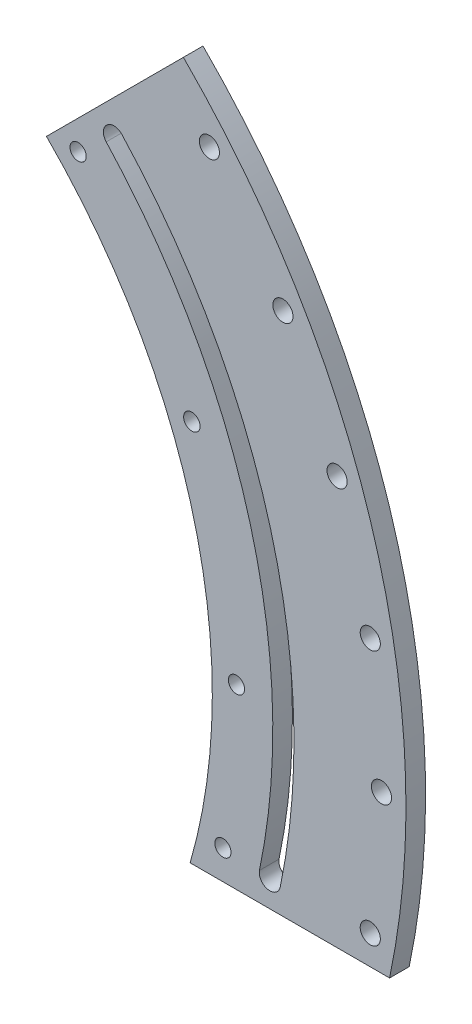
SolidWorks part; units mm, degrees
material "6061-T6 (SS)"
ref_plane "Front Plane" through (0, 0, 0) normal (0, 0, 1) x (1, 0, 0)
ref_plane "Top Plane" through (0, 0, 0) normal (0, 1, 0) x (1, 0, 0)
ref_plane "Right Plane" through (0, 0, 0) normal (1, 0, 0) x (0, 0, -1)
sketch "Sketch1" plane through (0, 0, 0) normal (0, 0, 1) x (1, 0, 0)
  line L0 (0, 0) -> (177.8, 0) construction
  line L1 (177.8, 0) -> (183.3563, 0) construction
  line L2 (0, 0) -> (191.1772, 6.6761) construction
  line L3 (0, 0) -> (182.7798, 182.7798) construction
  line L4 (184.7031, 10.1184) -> (184.959, 2.7905) construction
  line L5 (184.959, 2.7905) -> (191.4331, -0.6518) construction
  line L6 (191.4331, -0.6518) -> (197.6513, 3.2337) construction
  line L7 (197.6513, 3.2337) -> (197.3954, 10.5616) construction
  line L8 (197.3954, 10.5616) -> (190.9213, 14.0039) construction
  line L9 (190.9213, 14.0039) -> (184.7031, 10.1184) construction
  line L10 (139.9034, 130.462) -> (0, 0) construction
  line L11 (0, 0) -> (176.7324, 73.2049) construction
  line L12 (183.3563, 0) -> (183.3563, -50.8) construction
  line L13 (176.1785, -50.8) -> (183.3563, -50.8) construction
  line L14 (0, 0) -> (186.7878, -41.275) construction
  line L15 (0, 0) -> (203.2, 0) construction
  line L16 (203.2, 0) -> (209.55, 0) construction
  line L17 (209.55, 0) -> (228.6, 0) construction
  line L18 (228.6, 0) -> (238.125, 0) construction
  line L19 (0, 0) -> (238.125, 0) construction
  line L20 (0, 0) -> (234.5073, 41.35) construction
  line L21 (176.1785, -50.8) -> (240.7615, -50.8)
  line L22 (0, 0) -> (238.125, 0) construction
  line L23 (0, 0) -> (234.5073, -41.35) construction
  line L24 (129.6524, 129.6524) -> (173.9925, 173.9925)
  line L25 (153.8492, 142.2731) -> (149.1871, 137.9618) construction
  line L26 (198.8628, -41.7593) -> (205.1195, -42.8625) construction
  arc A0 (183.3563, 0) -> (129.6524, 129.6524) centre (0, 0) ccw
  arc A1 (184.9438, 0) -> (130.775, 130.775) centre (0, 0) ccw construction
  circle A3 centre (191.1772, 6.6761) radius 6.35 construction
  circle A4 centre (191.1772, 6.6761) radius 2.6289
  circle A5 centre (139.9034, 130.462) radius 2.6289
  circle A6 centre (176.7324, 73.2049) radius 2.667
  arc A7 (183.3563, 0) -> (176.1785, -50.8) centre (0, 0) cw
  circle A8 centre (186.7878, -41.275) radius 2.6289
  arc A9 (203.2, 0) -> (143.6841, 143.6841) centre (0, 0) ccw construction
  arc A10 (209.55, 0) -> (148.1742, 148.1742) centre (0, 0) ccw construction
  arc A11 (228.6, 0) -> (161.6446, 161.6446) centre (0, 0) ccw construction
  arc A12 (238.125, 0) -> (168.3798, 168.3798) centre (0, 0) ccw construction
  circle A13 centre (238.125, 0) radius 3.2639
  circle A14 centre (234.5073, 41.35) radius 3.2639
  circle A15 centre (223.7643, 81.4435) radius 3.2639
  circle A16 centre (206.2223, 119.0625) radius 3.2639
  circle A17 centre (182.4143, 153.0638) radius 3.2639
  arc A18 (240.7615, -50.8) -> (173.9925, 173.9925) centre (0, 0) ccw
  circle A19 centre (234.5073, -41.35) radius 3.2639
  arc A20 (209.55, 0) -> (153.8492, 142.2731) centre (0, 0) ccw construction
  arc A21 (149.1871, 137.9618) -> (203.2, 0) centre (0, 0) cw construction
  arc A22 (209.55, 0) -> (205.1195, -42.8625) centre (0, 0) cw construction
  arc A23 (203.2, 0) -> (198.8628, -41.7593) centre (0, 0) cw construction
  arc A24 (153.8492, 142.2731) -> (149.1871, 137.9618) centre (151.5181, 140.1174) ccw construction
  arc A25 (205.1195, -42.8625) -> (198.8628, -41.7593) centre (201.9911, -42.3109) cw construction
  arc A26 (202.946, 0) -> (198.6134, -41.711) centre (0, 0) cw
  arc A27 (205.3689, -42.9106) -> (198.6134, -41.711) centre (201.9911, -42.3109) cw
  arc A28 (209.804, 0) -> (205.3689, -42.9106) centre (0, 0) cw
  arc A29 (209.804, 0) -> (154.0357, 142.4455) centre (0, 0) ccw
  arc A30 (154.0357, 142.4455) -> (149.0006, 137.7893) centre (151.5181, 140.1174) ccw
  arc A31 (149.0006, 137.7893) -> (202.946, 0) centre (0, 0) cw
  point P9 (135.2593, 126.1313)
  point P20 (170.8657, 70.7749)
  point P27 (179.0372, -39.5623)
  dimension "D3" = 1.5875
  dimension "D4" = 12.7
  dimension "D6" = 5.2578
  dimension "D8" = 5.2578
  dimension "D12" = 5.334
  dimension "D14" = 50.8
  dimension "D15" = 5.2578
  dimension "D19" = 6.35
  dimension "D20" = 19.05
  dimension "D22" = 6.5278
  dimension "D26" = 7.9375
  dimension "D30" = 7.9375
  dimension "D31" = 7.9375
  dimension "D33" = 183.3562
  dimension "D1" = 177.8
  dimension "D2" = 5.5562
  dimension "D5" = 2
  dimension "D7" = 45
  dimension "D9" = 6.35
  dimension "D10" = 2
  dimension "D11" = 22.5
  dimension "D13" = 6.35
  dimension "D16" = 9.525
  dimension "D17" = 7.9375
  dimension "D18" = 203.2
  dimension "D21" = 9.525
  dimension "D24" = 10
  dimension "D25" = 238.125
  dimension "D28" = 10
  dimension "D29" = 238.125
  dimension "D32" = 0.254
  dimension "D23" = 5
  dimension "D27" = 2
extrude "Boss-Extrude1" add sketch "Sketch1" along normal blind 6.35 contours L21 A18 L24 A0 A7 A19 A4 A5 A6 A8 A13 A14 A15 A16 A17 A22 A25 A23 A21 A24 A20 region at (184.0595, -26.0065, 0)
